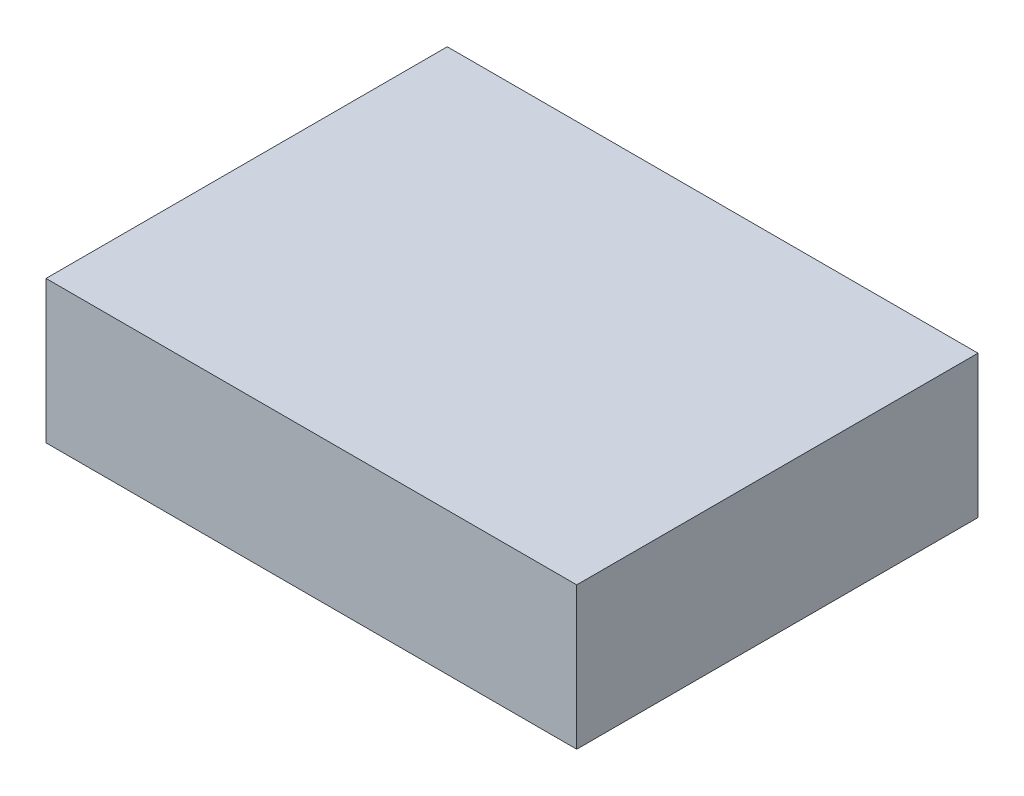
SolidWorks part; units mm, degrees
ref_plane "Front Plane" through (0, 0, 0) normal (0, 0, 1) x (1, 0, 0)
ref_plane "Top Plane" through (0, 0, 0) normal (0, 1, 0) x (1, 0, 0)
ref_plane "Right Plane" through (0, 0, 0) normal (1, 0, 0) x (0, 0, -1)
sketch "Sketch1" plane through (0, 0, 0) normal (0, -1, 0) x (1, 0, 0)
  line L0 (-31, 27.5826) -> (-31, 23)
  line L1 (31, 27.5826) -> (31, 77.7409)
  line L2 (-37.5826, 21) -> (-33, 21)
  line L3 (-37.5826, -21) -> (-4.1488, -21)
  line L4 (-35, -25) -> (-35, 25) construction
  line L5 (-35, 25) -> (35, 25) construction
  line L6 (35, 25) -> (35, -25) construction
  line L7 (35, -25) -> (-35, -25) construction
  line L10 (31.0164, 77.4853) -> (37.9804, 23.4428)
  line L11 (31, -23) -> (31, -56.5691)
  line L12 (33, -21) -> (66.328, -21)
  line L13 (-3.9593, -21.009) -> (-30.9487, -18.4402)
  arc A0 (-31, 27.5826) -> (-37.5826, 21) centre (-33, 23) ccw
  arc A1 (37.9804, 23.4428) -> (31, 27.5826) centre (33, 23) ccw
  arc A2 (-4.1488, -21) -> (-3.9593, -21.009) centre (-4.1488, -23) cw
  arc A3 (-37.5826, -21) -> (-30.9487, -18.4402) centre (-33, -23) ccw
  arc A4 (31, -56.5691) -> (66.328, -21) centre (33, -23.2267) ccw
  arc A5 (33, -21) -> (31, -23) centre (33, -23) ccw
  arc A6 (31, 77.7409) -> (31.0164, 77.4853) centre (33, 77.7409) ccw
  arc A7 (-31, 23) -> (-33, 21) centre (-33, 23) cw
  point P18 (31, -21)
  dimension "D1" = 10
  dimension "D2" = 10
  dimension "D3" = 10
  dimension "D4" = 2
  dimension "D5" = 4
  dimension "D6" = 4
  dimension "D7" = 4
  dimension "D8" = 4
extrude "Boss-Extrude1" add sketch "Sketch1" along normal blind 4 rebuild error yes
sketch "Sketch3" plane through (0, 28.9291, 0) normal (0, -1, 0) x (-1, 0, 0)
  line L0 (35, 25) -> (35, -25) construction
  line L1 (41, -31) -> (-41, -31)
  line L2 (41, -31) -> (41, 31)
  line L3 (41, 31) -> (-41, 31)
  line L4 (-41, -31) -> (-41, 31)
  line L5 (-35, -25) -> (-35, 25) construction
  line L6 (35, -25) -> (-35, -25) construction
  line L7 (-35, 25) -> (35, 25) construction
  dimension "D1" = 6
  dimension "D2" = 6
  dimension "D3" = 6
  dimension "D4" = 6
extrude "Boss-Extrude2" add sketch "Sketch3" against normal blind 22
